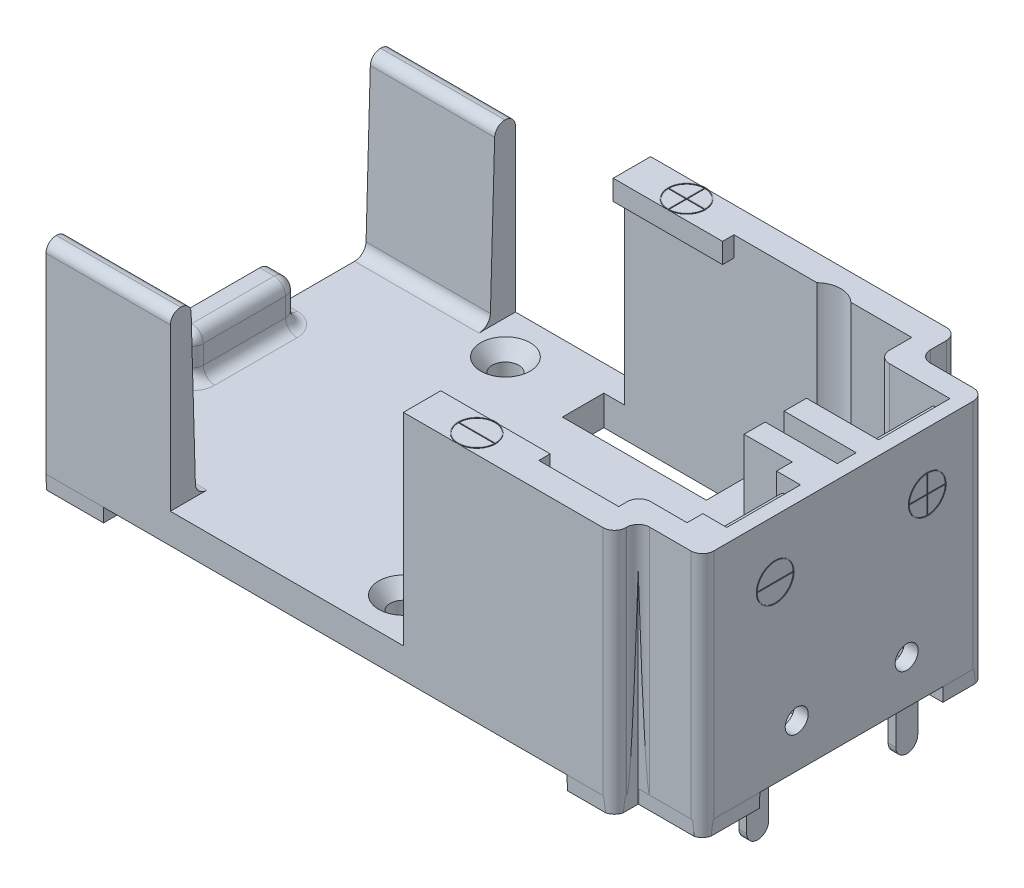
SolidWorks part; units mm, degrees
ref_plane "Front Plane" through (0, 0, 0) normal (0, 0, 1) x (1, 0, 0)
ref_plane "Top Plane" through (0, 0, 0) normal (0, 1, 0) x (1, 0, 0)
ref_plane "Right Plane" through (0, 0, 0) normal (1, 0, 0) x (0, 0, -1)
sketch "Sketch1" plane through (0, 0, 0) normal (0, 1, 0) x (1, 0, 0)
  line L0 (27.47, -14.985) -> (27.47, 14.985)
  line L1 (0, 0) -> (-27.47, 0) construction
  line L2 (0, 0) -> (0, 14.985) construction
  line L3 (27.47, 14.985) -> (-27.47, 14.985)
  line L4 (-27.47, -14.985) -> (-27.47, 14.985)
  line L5 (27.47, -14.985) -> (-27.47, -14.985)
  point P8 (27.47, 0)
  dimension "D1" = 27.47
  dimension "D2" = 14.985
extrude "Boss-Extrude1" add sketch "Sketch1" along normal blind 20.16
sketch "Sketch2" plane through (0, 20.16, 0) normal (0, 1, 0) x (1, 0, 0)
  line L1 (24.19, -3.2) -> (26.27, -3.2)
  line L2 (21.9, -14.985) -> (21.9, -12.9247)
  line L3 (27.47, -14.985) -> (27.47, 14.985) construction
  line L4 (26.27, -6.4) -> (17.0337, -6.4) construction
  line L5 (24.19, -3.2) -> (24.19, -1.8318)
  line L6 (20.01, -3.2) -> (26.27, -3.2) construction
  line L7 (24.19, -9.6) -> (24.19, -10.9682)
  line L8 (20.01, -10.96) -> (24.19, -10.9682)
  line L9 (21.9, -12.9247) -> (27.47, -12.9247)
  line L10 (20.01, -9.6) -> (20.01, -12.725) construction
  line L12 (0, 0) -> (40.166, 0) construction
  line L13 (20.01, 1.64) -> (26.27, 1.64)
  line L14 (25.21, -12.725) -> (25.21, 12.725)
  line L15 (-25.21, -12.725) -> (25.21, -12.725)
  line L16 (-25.21, 12.725) -> (-25.21, -12.725)
  line L17 (25.21, 12.725) -> (-25.21, 12.725)
  line L18 (26.27, 1.64) -> (26.27, 0)
  line L19 (3.57, -12.725) -> (20.01, -12.725)
  line L20 (27.47, 14.985) -> (-27.47, 14.985) construction
  line L21 (20.01, 12.725) -> (-4.93, 12.725)
  line L22 (20.01, 3.58) -> (20.01, 1.64)
  line L23 (27.47, 9.785) -> (-27.47, 9.785)
  line L24 (26.27, 9.785) -> (20.01, 9.785)
  line L25 (20.01, 3.58) -> (26.27, 3.58)
  line L26 (-4.93, 12.725) -> (-4.93, 14.985)
  line L27 (0, 3.58) -> (40.166, 3.58) construction
  line L28 (0, 1.64) -> (40.166, 1.64) construction
  line L29 (26.27, 3.58) -> (26.27, 9.785)
  line L30 (20.01, -10.96) -> (20.01, -12.725)
  line L31 (26.27, -3.2) -> (26.27, -9.6)
  line L32 (20.01, -1.84) -> (24.19, -1.8318)
  line L33 (20.01, 9.785) -> (20.01, 12.725)
  line L34 (26.27, -9.6) -> (24.19, -9.6)
  line L35 (20.01, -1.84) -> (20.01, 0)
  line L36 (20.01, 0) -> (26.27, 0)
  line L37 (-4.93, 9.785) -> (-4.93, 12.725) construction
  line L38 (-27.47, 14.985) -> (-27.47, -14.985) construction
  line L39 (-27.47, -14.985) -> (27.47, -14.985) construction
  line L40 (-4.93, 14.985) -> (-27.47, 14.985)
  line L41 (-27.47, 14.985) -> (-27.47, -14.985)
  line L42 (-27.47, -14.985) -> (3.57, -14.985)
  line L43 (3.57, -12.725) -> (3.57, -14.985)
  line L44 (3.57, -9.6) -> (3.57, -12.725) construction
  line L47 (21.9, -14.985) -> (27.47, -14.985)
  line L48 (27.47, -14.985) -> (27.47, -12.9247)
  line L49 (27.47, 11.605) -> (21.75, 11.605)
  line L50 (21.75, 11.605) -> (21.75, 14.985)
  line L51 (21.75, 9.785) -> (21.75, 12.725) construction
  line L52 (26.27, 11.605) -> (20.01, 11.605) construction
  line L53 (21.75, 14.985) -> (27.47, 14.985)
  line L54 (27.47, 14.985) -> (27.47, 11.605)
  point P1 (21.9, 14.985)
  point P3 (20.01, -14.3558)
  point P4 (20.05, 14.985)
  point P10 (27.47, 11.635)
  point P11 (-27.47, 11.635)
  dimension "D7" = 1.84
  dimension "D2" = 1.64
  dimension "D4" = 1.94
  dimension "D8" = 6.4
  dimension "D10" = 7.46
  dimension "D6" = 23.9
  dimension "D5" = 32.4
  dimension "D11" = 1.2
  dimension "D1" = 2.26
  dimension "D3" = 5.2
  dimension "D9" = 3.2
  dimension "D12" = 1.82
  dimension "D13" = 1.74
extrude "Cut-Extrude1" cut sketch "Sketch2" against normal offset from surface (17.56 mm away) 2.6
sketch "Sketch6" plane through (0, 2.6, 0) normal (0, 1, 0) x (1, 0, 0)
  line L4 (27.47, 14.985) -> (21.75, 14.985) construction
  line L5 (21.75, 14.985) -> (21.75, 11.605) construction
  line L6 (21.75, 11.605) -> (27.47, 11.605) construction
  line L7 (27.47, 11.605) -> (27.47, 14.985) construction
  line L12 (27.47, 14.985) -> (21.75, 14.985)
  line L13 (21.75, 14.985) -> (21.75, 11.605)
  line L14 (21.75, 11.605) -> (27.47, 11.605)
  line L15 (27.47, 11.605) -> (27.47, 14.985)
  line L16 (27.47, -14.985) -> (27.47, -12.9247)
  line L17 (27.47, -12.9247) -> (21.9, -12.9247)
  line L18 (21.9, -12.9247) -> (21.9, -14.985)
  line L19 (21.9, -14.985) -> (27.47, -14.985)
  line L20 (27.47, -14.985) -> (27.47, -12.9247)
  line L21 (27.47, -12.9247) -> (21.9, -12.9247)
  line L22 (21.9, -12.9247) -> (21.9, -14.985)
  line L23 (21.9, -14.985) -> (27.47, -14.985)
  dimension "D1" = 0
extrude "Cut-Extrude3" cut sketch "Sketch6" against normal through all
sketch "Sketch4" plane through (0, 0, 0) normal (0, -1, 0) x (1, 0, 0)
  line L0 (20.7508, 11.6747) -> (20.7508, 13.735)
  line L1 (21.75, -14.985) -> (17.7787, -14.985)
  line L2 (3.57, 9.985) -> (21.9, 9.985)
  line L3 (-27.47, 9.985) -> (-26.22, 9.985)
  line L4 (-22.47, 14.985) -> (-22.47, -14.985)
  line L6 (21.75, -11.605) -> (21.75, -14.985)
  line L7 (26.22, -7.9646) -> (26.22, -10.405)
  line L8 (26.22, 7.9247) -> (27.47, 7.9247)
  line L10 (17.7787, 13.735) -> (17.7787, 14.985)
  line L11 (0, 0) -> (45.1731, 0) construction
  line L12 (20.7508, 13.735) -> (17.7787, 13.735)
  line L13 (-0.24, 12.9247) -> (-0.24, -11.605) construction
  line L14 (21.75, -14.985) -> (21.75, -11.605) construction
  line L15 (21.75, -11.605) -> (27.47, -11.605) construction
  line L18 (-26.22, -13.735) -> (-22.47, -13.735)
  line L19 (27.47, -11.605) -> (27.47, -7.9646)
  line L20 (26.22, 11.6747) -> (20.7508, 11.6747)
  line L21 (-26.22, 13.735) -> (-26.22, 9.985)
  line L22 (21.75, -11.605) -> (27.47, -11.605)
  line L23 (0, 11.175) -> (45.1731, 11.175) construction
  line L24 (13.2474, 12.9247) -> (13.2474, -11.605) construction
  line L25 (21.9508, 12.9138) -> (27.47, 12.9138)
  line L26 (27.47, 12.9138) -> (27.47, 7.9247)
  line L27 (-22.47, 14.985) -> (-22.47, 13.735)
  line L28 (26.22, -10.405) -> (20.55, -10.405)
  line L29 (-22.47, -13.735) -> (-22.47, -14.985)
  line L30 (-26.22, -9.985) -> (-27.47, -9.985)
  line L31 (-22.47, -14.985) -> (-27.47, -14.985)
  line L32 (-27.47, -14.985) -> (-27.47, -9.985)
  line L33 (-27.47, 14.985) -> (-27.47, -14.985) construction
  line L34 (-22.47, 14.985) -> (-27.47, 14.985)
  line L35 (-27.47, 14.985) -> (-27.47, 9.985)
  line L36 (-26.22, -9.985) -> (-26.22, -13.735)
  line L37 (-22.47, 13.735) -> (-26.22, 13.735)
  line L38 (20.55, -13.735) -> (17.7787, -13.735)
  line L39 (26.22, 7.9247) -> (26.22, 11.6747)
  line L40 (17.7787, -13.735) -> (17.7787, -14.985)
  line L41 (21.9508, 12.9138) -> (21.9508, 14.985)
  line L42 (21.9508, 14.985) -> (17.7787, 14.985)
  line L48 (26.22, -7.9646) -> (27.47, -7.9646)
  line L49 (20.55, -10.405) -> (20.55, -13.735)
  circle A3 centre (-0.24, 11.175) radius 1.9
  circle A4 centre (-13.7274, -11.175) radius 1.9
  circle A5 centre (13.2474, -11.175) radius 1.9
  dimension "D5" = 13.4874
  dimension "D2" = 1.2
  dimension "D3" = 1.2
  dimension "D4" = 11.175
  dimension "D9" = 5
  dimension "D12" = 5
extrude "Boss-Extrude5" add sketch "Sketch4" along normal blind 1.2 draft 1
sketch "Sketch5" plane through (0, 2.6, 0) normal (0, 1, 0) x (1, 0, 0)
  line L1 (15.07, -12.725) -> (15.07, -9.125)
  line L2 (2.57, -12.9247) -> (2.57, 11.605)
  line L3 (2.57, -12.725) -> (2.57, -9.125)
  line L4 (5.77, 9.125) -> (5.77, 12.725)
  line L5 (15.07, -12.9247) -> (15.07, 11.605) construction
  line L6 (3.57, -9.125) -> (20.01, -9.125)
  line L7 (2.57, -9.125) -> (15.07, -9.125)
  line L8 (20.01, -12.725) -> (3.57, -12.725) construction
  line L9 (2.57, -12.9247) -> (2.57, 11.605) construction
  line L10 (15.07, -12.725) -> (2.57, -12.725)
  line L41 (-6.73, 9.125) -> (-6.73, 12.725)
  line L42 (-6.73, 12.725) -> (5.77, 12.725)
  line L43 (5.77, 9.125) -> (-6.73, 9.125)
  dimension "D1" = 24.9
  dimension "D2" = 12.5
  dimension "D3" = 3.6
extrude "Cut-Extrude4" cut sketch "Sketch5" against normal through all
sketch "Sketch7" plane through (0, 20.16, 0) normal (0, 1, 0) x (1, 0, 0)
  line L0 (21.75, 14.985) -> (-4.93, 14.985) construction
  line L1 (-4.93, 12.725) -> (-4.93, 14.985) construction
  line L3 (3.57, -14.985) -> (3.57, -12.725) construction
  line L5 (3.57, -14.985) -> (21.9, -14.985) construction
  line L6 (4.57, 14.985) -> (-4.93, 14.985)
  line L7 (-4.93, 11.735) -> (-4.93, 14.985)
  line L8 (-4.93, 12.725) -> (-4.93, 14.985) construction
  line L9 (3.57, -14.985) -> (3.57, -11.735)
  line L10 (3.57, -14.985) -> (3.57, -12.725) construction
  line L11 (3.57, -14.985) -> (13.07, -14.985)
  line L12 (4.57, 11.735) -> (4.57, 14.985)
  line L13 (13.07, -14.985) -> (13.07, -11.735)
  line L14 (4.57, 11.735) -> (-4.93, 11.735)
  line L15 (3.57, -11.735) -> (13.07, -11.735)
  line L16 (4.57, 12.725) -> (4.57, 14.985) construction
  line L17 (13.07, -14.985) -> (13.07, -12.725) construction
  dimension "D1" = 9.5
  dimension "D2" = 9.5
  dimension "D3" = 3.25
  dimension "D4" = 3.25
extrude "Boss-Extrude6" add sketch "Sketch7" against normal blind 1.75
sketch "Sketch8" plane through (0, -1.2, 0) normal (0, -1, 0) x (1, 0, 0)
  circle A0 centre (-0.24, 11.175) radius 1.145
  circle A1 centre (-13.7274, -11.175) radius 1.145
  circle A2 centre (13.2474, -11.175) radius 1.145
extrude "Cut-Extrude5" cut sketch "Sketch8" against normal through all
sketch "Sketch10" plane through (0, 20.16, 0) normal (0, 1, 0) x (1, 0, 0)
  circle A0 centre (13.2474, 11.175) radius 2.14
extrude "Cut-Extrude7" cut sketch "Sketch10" against normal up to surface (17.56 mm away) up to face at (13.2474, 2.6, -10.03)
chamfer "Chamfer1" distance 1 angle 50 3 edges at (-0.24, 2.6, 12.32) (13.2474, 2.6, -10.03) (-13.7274, 2.6, -10.03)
sketch "Sketch11" plane through (-27.47, 0, 0) normal (-1, 0, 0) x (0, 0, 1)
  line L1 (-14.985, 2.6) -> (-14.985, 16.61)
  line L2 (-9.985, 17.5) -> (9.985, 17.5)
  line L3 (-14.095, 17.5) -> (-14.0698, 17.5)
  line L4 (14.985, 2.6) -> (14.985, 16.61)
  line L5 (14.985, 2.6) -> (14.985, 20.16) construction
  line L6 (0, 0) -> (0, 24.7133) construction
  line L7 (12.785, 2.6) -> (13.1802, 16.6351)
  line L8 (14.0698, 17.5) -> (14.095, 17.5)
  line L9 (-14.985, 2.6) -> (-12.785, 2.6)
  line L10 (-12.785, 2.6) -> (-13.1802, 16.6351)
  line L11 (12.785, 2.6) -> (14.985, 2.6)
  arc A0 (14.985, 16.61) -> (14.095, 17.5) centre (14.095, 16.61) ccw
  arc A1 (-14.985, 16.61) -> (-14.095, 17.5) centre (-14.095, 16.61) cw
  arc A2 (13.1802, 16.6351) -> (14.0698, 17.5) centre (14.0698, 16.61) cw
  arc A3 (-13.1802, 16.6351) -> (-14.0698, 17.5) centre (-14.0698, 16.61) ccw
  point P17 (14.985, 17.5)
  dimension "D4" = 0.89
  dimension "D2" = 0.89
  dimension "D1" = 17.5
extrude "Boss-Extrude7" add sketch "Sketch11" against normal blind 10.8
sketch "Sketch12" plane through (-27.47, 0, 0) normal (-1, 0, 0) x (0, 0, 1)
  line L0 (0, 0) -> (0, 21.5428) construction
  line L1 (4.575, 2.6) -> (4.575, 6.23)
  line L2 (-4.575, 2.6) -> (-4.575, 6.23)
  line L4 (0, 2.6) -> (-4.575, 2.6)
  line L5 (-12.725, 6.23) -> (-9.785, 6.23)
  line L6 (-4.575, 6.23) -> (4.575, 6.23)
  line L7 (4.575, 0) -> (4.575, 21.5428) construction
  line L8 (-4.575, 0) -> (-4.575, 21.5428) construction
  line L9 (12.785, 2.6) -> (-12.785, 2.6) construction
  line L10 (-9.785, 2.6) -> (-3.58, 2.6) construction
  line L11 (0, 2.6) -> (4.575, 2.6)
  line L12 (9.6, 2.6) -> (3.2, 2.6) construction
  dimension "D1" = 4.575
  dimension "D2" = 4.575
  dimension "D3" = 3.63
extrude "Boss-Extrude8" add sketch "Sketch12" against normal blind 2.25
fillet "Fillet1" radius 1 8 edges at (-26.345, 2.6, 4.575) (-26.345, 6.23, 4.575) (-26.345, 6.23, -4.575) (-26.345, 2.6, -4.575) (-25.22, 4.415, 4.575) (-25.22, 4.415, -4.575) (-25.22, 6.23, 0) (-25.22, 2.6, 0)
fillet "Fillet2" radius 1 2 edges at (-22.07, 2.6, -12.785) (-22.07, 2.6, 12.785)
sketch "Sketch13" plane through (27.47, 0, 0) normal (1, 0, 0) x (0, 0, -1)
  line L5 (-7.9456, 3.8) -> (-12.8929, 3.8)
  line L6 (-4.7247, 3.8) -> (-12.8929, 3.8) construction
  line L7 (-4.7247, 0) -> (-4.7247, 20.16) construction
  line L9 (4.8253, 0) -> (4.8253, 20.16)
  line L10 (4.8253, 0) -> (4.8253, 20.16) construction
  circle A0 centre (-4.7247, 3.8) radius 1
  circle A1 centre (4.8253, 3.8) radius 1
  dimension "D3" = 17.75
  dimension "D2" = 5
extrude "Cut-Extrude8" cut sketch "Sketch13" against normal up to next
ref_plane "Plane1" through (0, 0, 6.4) normal (0, 0, 1) x (1, 0, 0)
sketch "Sketch14" plane through (0, 0, 6.4) normal (0, 0, 1) x (1, 0, 0)
  line L2 (20.67, 0) -> (20.67, 20.16)
  line L3 (20.67, 7.01) -> (20.67, 12.0372)
  line L5 (24.9004, 19.05) -> (20.67, 12.1788) construction
  line L6 (26.27, 0) -> (26.27, 19.05) construction
  line L8 (25.77, 0) -> (26.27, 0)
  line L9 (24.9004, 19.05) -> (26.27, 19.05) construction
  line L10 (24.7351, 18.7815) -> (20.7442, 12.2994)
  line L14 (25.1782, 19.05) -> (25.77, 19.05)
  line L15 (26.27, 0) -> (26.27, 20.16)
  line L16 (26.27, 0) -> (26.27, 18.55)
  line L19 (21.17, 7.01) -> (21.17, 12.0372)
  line L20 (3.57, 7.01) -> (21.9, 7.01)
  line L21 (20.67, 7.01) -> (21.17, 7.01)
  line L22 (25.1797, 18.55) -> (21.17, 12.0372)
  line L23 (25.1797, 18.55) -> (25.77, 18.55)
  line L24 (25.77, 0) -> (25.77, 18.55)
  line L26 (20.67, 0) -> (20.67, 12.1788) construction
  line L27 (21.17, 0) -> (21.17, 12.0372) construction
  arc A0 (20.7442, 12.2994) -> (20.67, 12.0372) centre (21.17, 12.0372) ccw
  arc A1 (26.27, 18.55) -> (25.77, 19.05) centre (25.77, 18.55) ccw
  arc A2 (24.7351, 18.7815) -> (25.1782, 19.05) centre (25.1782, 18.55) cw
  dimension "D2" = 0.5
  dimension "D1" = 6.8
  dimension "D5" = 1.2
  dimension "D6" = 13.15
  dimension "D7" = 0.5
extrude "Boss-Extrude9" add sketch "Sketch14" along normal blind 2.95 and the other way blind 2.95
pattern_linear "LPattern1" count 2 spacing 13.1 along (0, 0, -1) of "Boss-Extrude9"
fillet "Fillet3" radius 1 8 edges at (20.01, 11.38, -9.785) (20.01, 11.38, 10.96) (21.9, 10.08, 14.985) (21.9, 10.08, 12.9247) (27.47, 10.08, 12.9247) (27.47, 10.08, -11.605) (21.75, 10.08, -11.605) (21.75, 10.08, -14.985)
sketch "Sketch15" plane through (0, 20.16, 0) normal (0, 1, 0) x (1, 0, 0)
  line L0 (-0.18, 11.735) -> (-0.18, 14.985) construction
  line L1 (-4.93, 11.735) -> (4.57, 11.735) construction
  line L2 (20.75, 14.985) -> (-4.93, 14.985) construction
  line L3 (-0.155, 11.735) -> (-0.155, 11.7352)
  line L4 (-0.205, 11.735) -> (-0.205, 11.7352)
  line L5 (1.445, 13.36) -> (-1.805, 13.36) construction
  line L6 (1.445, 13.385) -> (1.4448, 13.385)
  line L7 (1.445, 13.335) -> (1.4448, 13.335)
  line L8 (-1.8048, 13.335) -> (-1.805, 13.335)
  line L9 (-1.8048, 13.385) -> (-1.805, 13.385)
  line L10 (1.445, 13.335) -> (-1.805, 13.335) construction
  line L11 (-0.205, 13.335) -> (-1.7548, 13.335)
  line L12 (1.445, 13.385) -> (-1.805, 13.385) construction
  line L13 (-0.205, 13.385) -> (-0.205, 14.9348)
  line L14 (-0.205, 13.385) -> (-1.7548, 13.385)
  line L15 (-0.205, 11.735) -> (-0.205, 14.985) construction
  line L16 (-0.155, 13.385) -> (-0.155, 14.9348)
  line L17 (1.3948, 13.335) -> (-0.155, 13.335)
  line L18 (-0.155, 11.735) -> (-0.155, 14.985) construction
  line L19 (1.3948, 13.385) -> (-0.155, 13.385)
  line L20 (-0.155, 14.9848) -> (-0.155, 14.985)
  line L21 (-0.205, 14.9848) -> (-0.205, 14.985)
  line L22 (-0.155, 11.7852) -> (-0.155, 13.335)
  line L23 (-0.205, 11.7852) -> (-0.205, 13.335)
  line L24 (8.295, -13.335) -> (8.345, -13.335)
  line L25 (9.8948, -13.335) -> (8.345, -13.335)
  line L26 (6.6952, -13.385) -> (6.695, -13.385)
  line L27 (8.295, -13.385) -> (8.345, -13.385)
  line L29 (8.295, -11.7352) -> (8.295, -11.735)
  line L31 (8.295, -14.985) -> (8.295, -14.9848)
  line L32 (9.945, -13.36) -> (6.695, -13.36) construction
  line L33 (9.945, -13.385) -> (9.9448, -13.385)
  line L34 (6.6952, -13.335) -> (6.695, -13.335)
  line L35 (8.345, -14.985) -> (8.345, -14.9848)
  line L36 (9.945, -13.335) -> (9.9448, -13.335)
  line L37 (9.8947, -13.385) -> (8.345, -13.385)
  line L38 (8.295, -13.385) -> (6.7448, -13.385)
  line L39 (8.345, -11.7352) -> (8.345, -11.735)
  line L40 (8.295, -13.335) -> (6.7448, -13.335)
  line L41 (8.32, -14.985) -> (8.32, -11.735) construction
  circle A0 centre (-0.18, 13.36) radius 1.625
  arc A1 (-1.7548, 13.335) -> (-0.205, 11.7852) centre (-0.18, 13.36) ccw
  arc A2 (1.3948, 13.385) -> (-0.155, 14.9348) centre (-0.18, 13.36) ccw
  circle A3 centre (-0.18, 13.36) radius 1.575 construction
  arc A4 (-0.205, 14.9348) -> (-1.7548, 13.385) centre (-0.18, 13.36) ccw
  arc A5 (-0.155, 11.7852) -> (1.3948, 13.335) centre (-0.18, 13.36) ccw
  arc A6 (6.7448, -13.385) -> (8.345, -14.9347) centre (8.3198, -13.3597) ccw
  circle A7 centre (8.32, -13.36) radius 1.625
  arc A8 (8.345, -14.9347) -> (9.8947, -13.385) centre (8.3198, -13.3597) ccw
  arc A9 (9.8948, -13.335) -> (8.345, -11.7847) centre (8.3198, -13.3597) ccw
  arc A10 (8.345, -11.7847) -> (6.7448, -13.335) centre (8.3198, -13.3597) ccw
  point P22 (1.395, 13.36)
  dimension "D1" = 0.05
  dimension "D2" = 0.025
  dimension "D3" = 0.025
  dimension "D4" = 0.025
  dimension "D5" = 0.025
extrude "Boss-Extrude10" add sketch "Sketch15" along normal blind 0.05 contours A7 A10 A9 L25 L24 L40 A8 A6 L38 L27 L37 | A0 A5 L22 L17 A4 L13 L14 A2 L19 L16 A1 L11 L23
sketch "Sketch16" plane through (27.47, 0, 0) normal (1, 0, 0) x (0, 0, -1)
  line L0 (6.6047, 13.535) -> (6.6047, 16.785) construction
  line L1 (6.6297, 13.535) -> (6.6297, 13.5352)
  line L2 (6.5797, 13.535) -> (6.5797, 13.5352)
  line L3 (8.2297, 15.16) -> (4.9797, 15.16) construction
  line L4 (8.2297, 15.185) -> (8.2295, 15.185)
  line L5 (8.2297, 15.135) -> (8.2295, 15.135)
  line L6 (4.9799, 15.135) -> (4.9797, 15.135)
  line L7 (4.9799, 15.185) -> (4.9797, 15.185)
  line L8 (6.5797, 15.135) -> (5.0299, 15.135)
  line L9 (6.5797, 15.185) -> (6.5797, 16.7348)
  line L10 (6.5797, 15.185) -> (5.0299, 15.185)
  line L11 (6.6297, 15.185) -> (6.6297, 16.7348)
  line L12 (8.1795, 15.135) -> (6.6297, 15.135)
  line L13 (8.1795, 15.185) -> (6.6297, 15.185)
  line L14 (6.6297, 16.7848) -> (6.6297, 16.785)
  line L15 (6.5797, 16.7848) -> (6.5797, 16.785)
  line L16 (6.6297, 13.5852) -> (6.6297, 15.135)
  line L17 (6.5797, 13.5852) -> (6.5797, 15.135)
  line L18 (0, 0) -> (0, 27.6495) construction
  line L19 (-8.2297, 15.16) -> (-4.9797, 15.16) construction
  line L20 (-11.9247, 15.16) -> (10.605, 15.16)
  line L21 (-11.9247, 15.16) -> (10.605, 15.16) construction
  line L22 (-6.6047, 13.535) -> (-6.6047, 16.785) construction
  line L23 (-6.6297, 15.135) -> (-6.5797, 15.135)
  line L24 (-6.6297, 15.185) -> (-6.5797, 15.185)
  line L25 (-6.5797, 16.7848) -> (-6.5797, 16.785)
  line L26 (-6.6297, 16.7848) -> (-6.6297, 16.785)
  line L27 (-8.1795, 15.185) -> (-6.6297, 15.185)
  line L28 (-8.1795, 15.135) -> (-6.6297, 15.135)
  line L29 (-6.6297, 16.7348) -> (-6.5797, 16.7348)
  line L30 (-6.5797, 15.185) -> (-5.0299, 15.185)
  line L31 (-6.6297, 13.5852) -> (-6.5797, 13.5852)
  line L32 (-6.5797, 15.135) -> (-5.0299, 15.135)
  line L33 (-4.9799, 15.185) -> (-4.9797, 15.185)
  line L34 (-4.9799, 15.135) -> (-4.9797, 15.135)
  line L35 (-8.2297, 15.135) -> (-8.2295, 15.135)
  line L36 (-8.2297, 15.185) -> (-8.2295, 15.185)
  line L37 (-6.5797, 13.535) -> (-6.5797, 13.5352)
  line L38 (-6.6297, 13.535) -> (-6.6297, 13.5352)
  circle A0 centre (6.6047, 15.16) radius 1.625
  arc A1 (5.0299, 15.135) -> (6.5797, 13.5852) centre (6.6047, 15.16) ccw
  arc A2 (8.1795, 15.185) -> (6.6297, 16.7348) centre (6.6047, 15.16) ccw
  arc A3 (6.5797, 16.7348) -> (5.0299, 15.185) centre (6.6047, 15.16) ccw
  arc A4 (6.6297, 13.5852) -> (8.1795, 15.135) centre (6.6047, 15.16) ccw
  arc A5 (-6.6297, 13.5852) -> (-8.1795, 15.135) centre (-6.6047, 15.16) cw
  arc A6 (-6.5797, 16.7348) -> (-5.0299, 15.185) centre (-6.6047, 15.16) cw
  arc A7 (-8.1795, 15.185) -> (-6.6297, 16.7348) centre (-6.6047, 15.16) cw
  arc A8 (-5.0299, 15.135) -> (-6.5797, 13.5852) centre (-6.6047, 15.16) cw
  circle A9 centre (-6.6047, 15.16) radius 1.625
  dimension "D1" = 5
extrude "Boss-Extrude11" add sketch "Sketch16" along normal blind 0.05 contours A0 A4 L16 L12 A3 L9 L10 A2 L13 L11 A1 L8 L17 | A9 L27 A7 L29 A6 L30 L24 L32 A8 L31 A5 L28 L23
sketch "Sketch17" plane through (25.77, 0, 0) normal (-1, 0, 0) x (0, 0, 1)
  line L0 (6.4, 2.6) -> (6.4, 23.6187) construction
  line L1 (3.45, 2.6) -> (9.35, 2.6) construction
  line L2 (7.4, 2.6) -> (7.4, 4.1)
  line L3 (5.4, 2.6) -> (5.4, 4.1)
  line L5 (3.45, 18.55) -> (3.45, 2.6) construction
  line L6 (11.8128, 4.6) -> (5.575, 4.6)
  line L7 (9.35, 4.6) -> (7.9, 4.6)
  line L8 (9.35, 18.55) -> (9.35, 2.6) construction
  line L9 (3.45, 4.6) -> (3.45, 2.6)
  line L10 (9.35, 4.6) -> (9.35, 2.6)
  line L11 (4.9, 4.6) -> (3.45, 4.6)
  line L12 (7.4, 2.6) -> (7.4, 23.6187) construction
  line L13 (5.4, 2.6) -> (5.4, 23.6187) construction
  line L14 (3.45, 2.6) -> (5.4, 2.6)
  line L15 (7.4, 2.6) -> (9.35, 2.6)
  line L16 (-6.7, 2.6) -> (-6.7, 22.2829) construction
  line L17 (-9.65, 2.6) -> (-3.75, 2.6) construction
  line L18 (-3.75, 4.6) -> (-5.2, 4.6)
  line L19 (-7.7, 2.6) -> (-7.7, 4.1)
  line L20 (-3.75, 4.6) -> (-3.75, 2.6)
  line L21 (-8.2, 4.6) -> (-9.65, 4.6)
  line L22 (-5.7, 2.6) -> (-3.75, 2.6)
  line L23 (-5.7, 2.6) -> (-5.7, 4.1)
  line L24 (-9.65, 2.6) -> (-7.7, 2.6)
  line L25 (-9.65, 4.6) -> (-9.65, 2.6)
  arc A0 (7.4, 4.1) -> (7.9, 4.6) centre (7.9, 4.1) cw
  arc A1 (5.4, 4.1) -> (4.9, 4.6) centre (4.9, 4.1) ccw
  arc A2 (-7.7, 4.1) -> (-8.2, 4.6) centre (-8.2, 4.1) ccw
  arc A3 (-5.7, 4.1) -> (-5.2, 4.6) centre (-5.2, 4.1) cw
  point P22 (5.4, 4.6)
  dimension "D4" = 0.5
  dimension "D1" = 1
  dimension "D2" = 1
  dimension "D3" = 2
extrude "Cut-Extrude9" cut sketch "Sketch17" against normal blind 0.5
sketch "Sketch18" plane through (0, 0, 0) normal (0, -1, 0) x (1, 0, 0)
  line L0 (13.2474, -11.175) -> (37.7716, -11.175) construction
  line L1 (13.2474, -6.435) -> (37.7716, -6.435) construction
  line L2 (13.2474, 6.515) -> (37.7716, 6.515) construction
  line L3 (13.2474, -11.175) -> (13.2474, 26.6117) construction
  line L4 (25.5374, -11.175) -> (25.5374, 26.6117) construction
  line L5 (25.8674, -7.39) -> (25.8674, -5.48)
  line L6 (25.2074, -7.39) -> (25.2074, -5.48)
  line L7 (25.2074, 5.56) -> (25.8674, 5.56)
  line L8 (25.2074, -7.39) -> (25.8674, -7.39)
  line L9 (25.2074, 7.47) -> (25.8674, 7.47)
  line L10 (25.2074, -5.48) -> (25.8674, -5.48)
  line L11 (25.8674, 5.56) -> (25.8674, 7.47)
  line L12 (13.2474, 5.56) -> (37.7716, 5.56) construction
  line L13 (13.2474, 7.47) -> (37.7716, 7.47) construction
  line L14 (25.2074, -11.175) -> (25.2074, 26.6117) construction
  line L15 (25.8674, -11.175) -> (25.8674, 26.6117) construction
  line L16 (25.2074, 5.56) -> (25.2074, 7.47)
  line L18 (13.2474, -5.48) -> (37.7716, -5.48) construction
  line L19 (13.2474, -7.39) -> (37.7716, -7.39) construction
  dimension "D1" = 4.74
  dimension "D2" = 12.95
  dimension "D3" = 12.29
  dimension "D4" = 0.33
  dimension "D5" = 0.33
  dimension "D6" = 0.955
  dimension "D7" = 0.955
extrude "Boss-Extrude12" add sketch "Sketch18" along normal blind 5.08
fillet "Fillet4" radius 0.95 4 edges at (25.5374, -5.08, -7.39) (25.5374, -5.08, 5.56) (25.5374, -5.08, 7.47) (25.5374, -5.08, -5.48)
